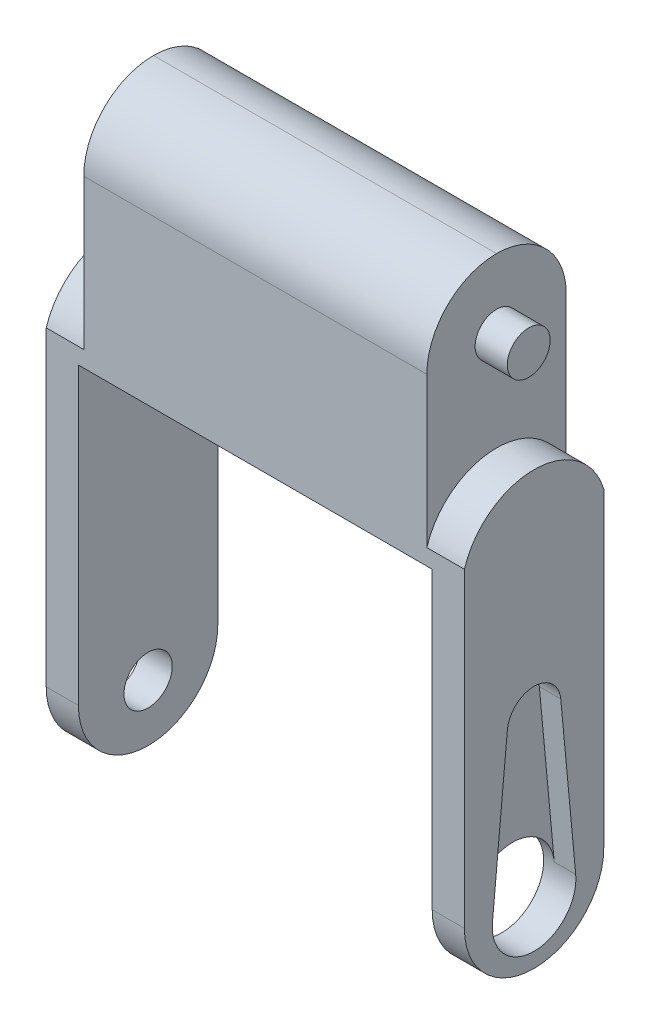
SolidWorks part; units mm, degrees
ref_plane "Plano frontal" through (0, 0, 0) normal (0, 0, 1) x (1, 0, 0)
ref_plane "Plano superior" through (0, 0, 0) normal (0, 1, 0) x (1, 0, 0)
ref_plane "Plano direito" through (0, 0, 0) normal (1, 0, 0) x (0, 0, -1)
sketch "Sketch1" plane through (0, 0, 0) normal (0, 0, 1) x (1, 0, 0)
  line L0 (3, 0) -> (3, 34)
  line L1 (0, 0) -> (3, 0)
  line L2 (0, 0) -> (0, 42)
  line L3 (3.5, 56) -> (35.5, 56)
  line L4 (39, 0) -> (39, 42)
  line L5 (3, 34) -> (36, 34)
  line L6 (36, 34) -> (36, 0)
  line L7 (36, 0) -> (39, 0)
  line L8 (0, 42) -> (3.5, 42)
  line L9 (3.5, 42) -> (3.5, 56)
  line L10 (35.5, 56) -> (35.5, 42)
  line L11 (35.5, 42) -> (39, 42)
  dimension "D1" = 39
  dimension "D2" = 56
  dimension "D3" = 3
  dimension "D4" = 3
  dimension "D5" = 22
  dimension "D6" = 14
  dimension "D7" = 14
  dimension "D8" = 3.5
  dimension "D9" = 32
extrude "Boss-Extrude1" add sketch "Sketch1" along normal blind 13
sketch "Sketch2" plane through (0, 0, 0) normal (-1, 0, 0) x (0, 0, 1)
  circle A0 centre (6.5, 5.294) radius 2.25
  dimension "D1" = 4.5
extrude "Cut-Extrude1" cut sketch "Sketch2" against normal blind 3
sketch "Sketch3" plane through (3.5, 0, 0) normal (-1, 0, 0) x (0, 0, 1)
  line L0 (13, 56) -> (0, 56) construction
  circle A0 centre (6.5, 49.5) radius 2
  dimension "D1" = 4
  dimension "D2" = 6.5
extrude "Boss-Extrude2" add sketch "Sketch3" along normal blind 3
sketch "Sketch4" plane through (35.5, 0, 0) normal (1, 0, 0) x (0, 0, -1)
  line L0 (-13, 56) -> (0, 56) construction
  circle A0 centre (-6.5, 49.5) radius 2
  dimension "D1" = 4
  dimension "D2" = 6.5
extrude "Boss-Extrude3" add sketch "Sketch4" along normal blind 3
sketch "Sketch5" plane through (39, 0, 0) normal (1, 0, 0) x (0, 0, -1)
  line L1 (0, 35.5) -> (0, 45)
  line L2 (0, 42) -> (0, 56) construction
  line L3 (0, 45) -> (-13, 45)
  line L4 (-13, 42) -> (-13, 56) construction
  line L5 (-13, 45) -> (-13, 35.5)
  line L6 (-13, 42) -> (0, 42) construction
  arc A1 (-13, 35.5) -> (0, 35.5) centre (-6.5, 33.5) cw
  dimension "D1" = 3
  dimension "D2" = 9.5
  dimension "D3" = 6.8007
extrude "Cut-Extrude2" cut sketch "Sketch5" against normal up to surface (3.5 mm away) up to face at (35.5, 47.5, 6.5)
sketch "Sketch6" plane through (0, 0, 0) normal (-1, 0, 0) x (0, 0, 1)
  line L0 (13, 42) -> (0, 42) construction
  line L1 (13, 35.5) -> (13, 45)
  line L3 (13, 45) -> (0, 45)
  line L5 (0, 45) -> (0, 35.5)
  arc A0 (0, 35.5) -> (13, 35.5) centre (6.5, 33.5) cw
  dimension "D1" = 9.5
  dimension "D2" = 6.8007
  dimension "D3" = 3
extrude "Cut-Extrude3" cut sketch "Sketch6" against normal up to surface (3.5 mm away) up to face at (3.5, 49.5, 4.5)
fillet "Fillet1" radius 6.5 2 edges at (19.5, 56, 13) (19.5, 56, 0)
fillet "Fillet2" radius 6.5 4 edges at (37.5, 0, 13) (37.5, 0, 0) (1.5, 0, 13) (1.5, 0, 0)
sketch "Sketch7" plane through (36, 0, 0) normal (-1, 0, 0) x (0, 0, 1)
  circle A0 centre (6.5, 5.294) radius 3.9
  dimension "D1" = 7.8
extrude "Cut-Extrude4" cut sketch "Sketch7" against normal through all
sketch "Sketch8" plane through (39, 0, 0) normal (1, 0, 0) x (0, 0, -1)
  line L0 (-6.5, 20.294) -> (-6.5, 5.294) construction
  line L1 (-8.9891, 20.5273) -> (-10.383, 5.658)
  line L2 (-2.617, 5.658) -> (-4.0109, 20.5273)
  arc A0 (-4.0109, 20.5273) -> (-8.9891, 20.5273) centre (-6.5, 20.294) ccw
  circle A1 centre (-6.5, 5.294) radius 3.9 construction
  arc A2 (-10.383, 5.658) -> (-2.617, 5.658) centre (-6.5, 5.294) ccw
  dimension "D1" = 5
  dimension "D2" = 15
extrude "Cut-Extrude5" cut sketch "Sketch8" against normal blind 2
